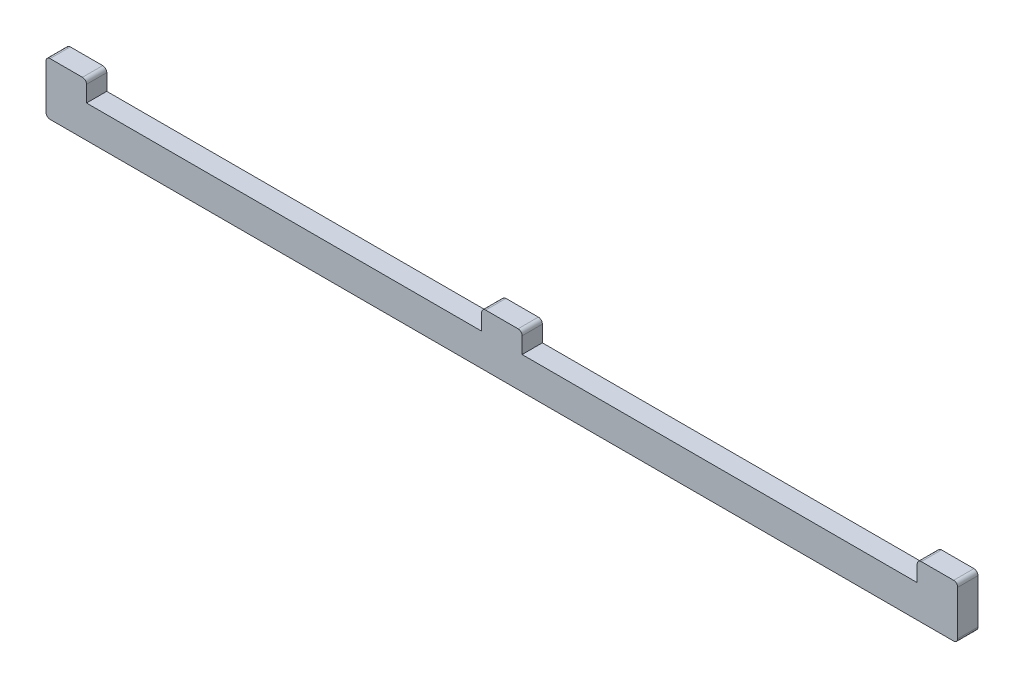
SolidWorks part; units mm, degrees
ref_plane "Front" through (0, 0, 0) normal (0, 0, 1) x (1, 0, 0)
ref_plane "Top" through (0, 0, 0) normal (0, 1, 0) x (1, 0, 0)
ref_plane "Right" through (0, 0, 0) normal (1, 0, 0) x (0, 0, -1)
sketch "Sketch1" plane through (0, 0, 0) normal (0, 0, 1) x (1, 0, 0)
  line L0 (117.5, 8) -> (215, 8)
  line L1 (1, 0) -> (224, 0)
  line L2 (0, 1) -> (0, 8)
  line L3 (10, 8) -> (107.5, 8)
  line L4 (225, 1) -> (225, 5)
  line L6 (107.5, 8) -> (107.5, 12)
  line L7 (108.5, 13) -> (116.5, 13)
  line L8 (117.5, 8) -> (117.5, 12)
  line L11 (0, 8) -> (0, 12)
  line L12 (1, 13) -> (9, 13)
  line L13 (10, 8) -> (10, 12)
  line L15 (225, 5) -> (225, 12)
  line L16 (224, 13) -> (216, 13)
  line L17 (215, 8) -> (215, 12)
  arc A0 (225, 1) -> (224, 0) centre (224, 1) cw
  arc A1 (1, 0) -> (0, 1) centre (1, 1) cw
  arc A2 (117.5, 12) -> (116.5, 13) centre (116.5, 12) ccw
  arc A3 (108.5, 13) -> (107.5, 12) centre (108.5, 12) ccw
  arc A4 (10, 12) -> (9, 13) centre (9, 12) ccw
  arc A5 (1, 13) -> (0, 12) centre (1, 12) ccw
  arc A6 (225, 12) -> (224, 13) centre (224, 12) ccw
  arc A7 (216, 13) -> (215, 12) centre (216, 12) ccw
  point P11 (225, 0)
  point P14 (0, 0)
  point P17 (117.5, 13)
  point P20 (107.5, 13)
  point P29 (10, 13)
  point P32 (0, 13)
  point P35 (225, 13)
  point P38 (215, 13)
  dimension "D6" = 1
  dimension "D11" = 1
  dimension "D1" = 8
  dimension "D2" = 225
  dimension "D3" = 107.5
  dimension "D4" = 10
  dimension "D5" = 5
  dimension "D7" = 10
  dimension "D8" = 5
  dimension "D9" = 5
  dimension "D10" = 10
  dimension "D12" = 8
extrude "Boss-Extrude1" add sketch "Sketch1" along normal blind 5
